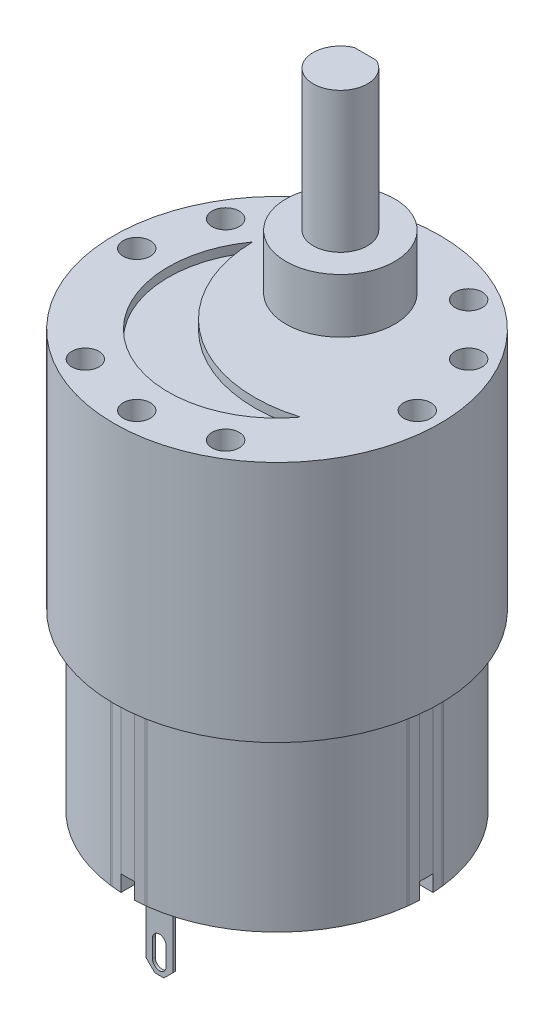
SolidWorks part; units mm, degrees
ref_plane "Front Plane" through (0, 0, 0) normal (0, 0, 1) x (1, 0, 0)
ref_plane "Top Plane" through (0, 0, 0) normal (0, 1, 0) x (1, 0, 0)
ref_plane "Right Plane" through (0, 0, 0) normal (1, 0, 0) x (0, 0, -1)
sketch "Sketch4" plane through (0, 0, 0) normal (0, 1, 0) x (1, 0, 0)
  line L0 (1.199, 9.75) -> (-1.199, 9.75)
  line L1 (6.3399, -16.8465) -> (6.3402, -16.8475)
  line L2 (5.6036, -17.1055) -> (5.6039, -17.1065)
  line L3 (-1.891, -17.9004) -> (-1.8911, -17.9014)
  line L4 (-1.2513, -17.9565) -> (-1.2514, -17.9575)
  line L5 (7.6212, -16.307) -> (7.6216, -16.3079)
  line L6 (-7.4709, -16.3764) -> (-7.4713, -16.3773)
  line L7 (-5.9708, -16.9809) -> (-5.9711, -16.9818)
  line L8 (-3.5022, -17.656) -> (-3.5024, -17.657)
  line L9 (5.1061, -17.2606) -> (5.1064, -17.2616)
  line L10 (-9.1333, -15.5115) -> (-9.1335, -15.5118)
  line L11 (-8.2134, -16.0169) -> (-8.2138, -16.0178)
  line L12 (-5.5614, -17.1193) -> (-5.5617, -17.1203)
  line L13 (-2.0114, -17.8883) -> (-1.9309, -17.8968)
  line L14 (-2.1464, -17.8726) -> (-2.0114, -17.8883)
  line L15 (5.1226, -17.2557) -> (5.1229, -17.2566)
  line L16 (-3.6114, -17.635) -> (-3.5453, -17.6481)
  line L17 (-5.5496, -17.1231) -> (-5.5499, -17.1241)
  line L18 (-0.9209, -17.9764) -> (-0.921, -17.9774)
  line L19 (5.5426, -17.1254) -> (5.5429, -17.1264)
  line L20 (-2.763, -17.7877) -> (-2.7337, -17.7922)
  line L21 (3.3885, -17.6792) -> (3.4863, -17.66)
  line L22 (3.3594, -17.6848) -> (3.3885, -17.6792)
  line L23 (-9.4676, -15.3101) -> (-9.4487, -15.3218)
  circle A0 centre (0, 7) radius 6
  circle A1 centre (7.75, -13.4234) radius 1.5
  circle A2 centre (7.75, 13.4234) radius 1.5
  circle A3 centre (15.5, 0) radius 1.5
  circle A4 centre (0, 0) radius 18
  circle A5 centre (-15.5, 0) radius 1.5
  circle A6 centre (-7.75, -13.4234) radius 1.5
  circle A7 centre (-13.4234, 7.75) radius 1.5
  circle A8 centre (0, -15.5) radius 1.5
  circle A9 centre (-7.75, 13.4234) radius 1.5
  circle A10 centre (13.4234, 7.75) radius 1.5
  arc A11 (-1.199, 9.75) -> (1.199, 9.75) centre (0, 7) ccw
  arc A12 (1.199, 9.75) -> (-1.199, 9.75) centre (0, 7) ccw
  arc A13 (-9.7223, 7.034) -> (9.6912, -7.0767) centre (5.276, 7.2587) ccw
  arc A14 (-9.7223, 7.034) -> (9.6912, -7.0767) centre (0, 0) ccw
  arc A15 (-5.0637, -17.2741) -> (-4.2837, -17.4839) centre (0, 0) ccw
  arc A16 (-0.4816, -17.9946) -> (1.4509, -17.9424) centre (0, 0) ccw
  arc A17 (3.483, -17.6608) -> (5.1064, -17.2616) centre (0, 0) ccw
  arc A18 (-9.1335, -15.5118) -> (-8.2138, -16.0178) centre (0, 0) ccw
  arc A19 (-6.5915, -16.7508) -> (-5.5499, -17.1241) centre (0, 0) ccw
  arc A20 (1.7855, -17.9122) -> (2.9289, -17.7611) centre (0, 0) ccw
  arc A21 (5.9059, -17.0046) -> (7.2979, -16.4553) centre (0, 0) ccw
  spline S0 degree 3 poles (6.3402, -16.8475) (6.6068, -16.7471) (6.813, -16.6627) (6.961, -16.6005) knots 0 0 0 0 0.5 0.5 0.5 0.5
  spline S1 degree 2 poles (6.961, -16.6005) (7.1091, -16.5384) (7.1825, -16.506) knots 0.5 0.5 0.5 1 1 1
  spline S2 degree 3 poles (5.6039, -17.1065) (5.6837, -17.0803) (5.7951, -17.0433) (6.0796, -16.944) (6.2138, -16.895) (6.3402, -16.8475) knots 0 0 0 0 0.5 0.5 1 1 1 1
  spline S3 degree 3 poles (-2.68, -17.8004) (-2.5921, -17.8136) (-2.4727, -17.831) (-2.1706, -17.8703) (-2.027, -17.887) (-1.8911, -17.9014) knots 0 0 0 0 0.5 0.5 1 1 1 1
  spline S4 degree 3 poles (-1.8911, -17.9014) (-1.616, -17.9305) (-1.4189, -17.9458) (-1.2514, -17.9575) knots 0 0 0 0 1 1 1 1
  spline S5 degree 3 poles (8.4939, -15.871) (8.7886, -15.7133) (9.0012, -15.5896) (9.1367, -15.5098) knots 0 0 0 0 0.5 0.5 0.5 0.5
  spline S6 degree 2 poles (9.1367, -15.5098) (9.2722, -15.43) (9.3392, -15.3888) knots 0.5 0.5 0.5 1 1 1
  spline S7 degree 2 poles (7.6216, -16.3079) (7.6938, -16.2747) (7.8368, -16.2055) knots 0 0 0 0.5 0.5 0.5
  spline S8 degree 3 poles (7.8368, -16.2055) (7.9799, -16.1363) (8.2006, -16.028) (8.4939, -15.871) knots 0.5 0.5 0.5 0.5 1 1 1 1
  spline S9 degree 3 poles (-6.5017, -16.7858) (-6.3083, -16.8607) (-6.1327, -16.925) (-5.9711, -16.9818) knots 0 0 0 0 1 1 1 1
  spline S10 degree 3 poles (-4.2837, -17.4839) (-4.0726, -17.5356) (-3.9134, -17.5707) (-3.701, -17.6168) (-3.5993, -17.6378) (-3.5024, -17.657) knots 0 0 0 0 0.5 0.5 1 1 1 1
  spline S11 degree 3 poles (-5.9711, -16.9818) (-5.9059, -17.0047) (-5.8335, -17.0298) (-5.6744, -17.0835) (-5.6102, -17.1045) (-5.5617, -17.1203) knots 0 0 0 0 0.5 0.5 1 1 1 1
  spline S12 degree 2 poles (-1.2514, -17.9575) (-1.0739, -17.9698) (-0.9802, -17.9743) knots 0 0 0 1 1 1
  spline S13 degree 2 poles (-3.5024, -17.657) (-3.286, -17.6999) (-3.1918, -17.7158) knots 0 0 0 1 1 1
  spline S14 degree 2 poles (-7.8335, -16.2072) (-7.7051, -16.2707) (-7.4713, -16.3773) knots 0 0 0 1 1 1
  spline S15 degree 3 poles (-1.4938, -17.9389) (-1.4929, -17.939) (-1.4674, -17.9412) (-1.4343, -17.9438) (-1.3992, -17.9465) (-1.396, -17.9468) (-1.3942, -17.9469) knots 0 0 0 0 0.010494 0.320794 0.64482 1 1 1 1
  spline S16 degree 3 poles (6.7071, -16.7048) (6.7312, -16.6951) (6.7877, -16.6723) (6.7956, -16.669) (6.8001, -16.6672) knots 0 0 0 0 0.427084 1 1 1 1
  spline S17 degree 3 poles (-3.1918, -17.7158) (-3.1514, -17.7229) (-3.0644, -17.7384) (-3.0555, -17.7398) (-3.0507, -17.7406) knots 0 0 0 0 0.463237 1 1 1 1
  spline S18 degree 3 poles (-9.4487, -15.3218) (-9.3817, -15.3629) (-9.2797, -15.4255) (-9.1707, -15.4895) (-9.1333, -15.5115) knots 0 0 0 0 0.656855 1 1 1 1
extrude "Boss-Extrude1" add sketch "Sketch4" against normal blind 26.8 contours A13 A14 | A5 | A7 | A9 | A10 | A2 | A3 | A1 | A8 | A6 | A4 A14 A13 A10 A9 A8 A7 A6 A5 A0 A1 A2 A3 | A0 A12 A11 | L0 A11 | L0 A12 region at (0, 0, -6.9588) region at (0, 0, -9.8504) region at (0.7413, 0, 0.0854) region at (-5.8303, 0, -7) region at (7.75, 0, 13.4234) region at (7.75, 0, -13.4234) region at (15.5, 0, 0) region at (-15.5, 0, 0) region at (-7.75, 0, 13.4234) region at (-13.4234, 0, -7.75) region at (0, 0, 15.5) region at (-7.75, 0, -13.4234) region at (13.4234, 0, -7.75) region at (-4.2506, 0, 5.8479)
extrude "Cut-Extrude1" cut sketch "Sketch4<4>" against normal blind 1 contours A13 A14
sketch "Sketch4<4>" plane through (0, 0, 0) normal (0, 1, 0) x (1, 0, 0) same geometry as "Sketch4"
extrude "Boss-Extrude2" add sketch "Sketch4<5>" along normal blind 6 separate body contours A0 A12 A11 region at (-5.8303, 0, -7)
sketch "Sketch4<5>" plane through (0, 0, 0) normal (0, 1, 0) x (1, 0, 0) same geometry as "Sketch4"
extrude "Boss-Extrude3" add sketch "Sketch4<7>" along normal blind 9.5 contours L0 A12 region at (0, 0, -9.8504)
sketch "Sketch4<7>" plane through (0, 0, 0) normal (0, 1, 0) x (1, 0, 0) same geometry as "Sketch4"
extrude "Boss-Extrude4" add sketch "Sketch4<8>" along normal blind 21.5 contours L0 A11 region at (0, 0, -6.9588)
sketch "Sketch4<8>" plane through (0, 0, 0) normal (0, 1, 0) x (1, 0, 0) same geometry as "Sketch4"
sketch "Sketch5" plane through (0, -26.8, 0) normal (0, -1, 0) x (1, 0, 0)
  line L0 (0.75, -16.4829) -> (1.8083, -16.4006)
  line L1 (1.8083, -16.4006) -> (2, -16.3783)
  line L2 (16.3783, -2) -> (16.4006, -1.8083)
  line L3 (16.4006, -1.8083) -> (16.4829, -0.75)
  line L4 (-16.4829, -0.75) -> (-16.4006, -1.8083)
  line L5 (-16.4006, -1.8083) -> (-16.3783, -2)
  line L6 (-2, -16.3783) -> (-1.8083, -16.4006)
  line L7 (-1.8083, -16.4006) -> (-0.75, -16.4829)
  line L8 (-0.75, 16.4829) -> (-1.8083, 16.4006)
  line L9 (-1.8083, 16.4006) -> (-2, 16.3783)
  line L10 (-16.3783, 2) -> (-16.4006, 1.8083)
  line L11 (-16.4006, 1.8083) -> (-16.4829, 0.75)
  line L12 (16.4829, 0.75) -> (16.4006, 1.8083)
  line L13 (16.4006, 1.8083) -> (16.3783, 2)
  line L14 (2, 16.3783) -> (1.8083, 16.4006)
  line L15 (1.8083, 16.4006) -> (0.75, 16.4829)
  line L16 (-3.3, 0) -> (-3.5, 0)
  line L17 (-1.5, 13) -> (-1.5, 12.7)
  line L18 (1.5, 13) -> (-1.5, 13)
  line L19 (-0.5, 12.7) -> (-0.5, 13)
  line L20 (-1.5, 12.7) -> (1.5, 12.7)
  line L21 (-1.5, -12.7) -> (-1.5, -13)
  line L22 (-0.5, -13) -> (-0.5, -12.7)
  line L23 (-1.5, -13) -> (1.5, -13)
  line L24 (1.5, -12.7) -> (-1.5, -12.7)
  line L25 (0.5, 13) -> (0.5, 12.7)
  line L26 (0.5, -12.7) -> (0.5, -13)
  line L27 (1.5, -13) -> (1.5, -12.7)
  line L28 (1.5, 12.7) -> (1.5, 13)
  line L29 (13.5, -2) -> (13.5, 2)
  line L30 (16.3783, -2) -> (13.5, -2)
  line L31 (2, -13.5) -> (2, -16.3783)
  line L32 (-2, -13.5) -> (2, -13.5)
  line L33 (-2, -16.3783) -> (-2, -13.5)
  line L34 (-13.5, 2) -> (-13.5, -2)
  line L35 (-2, 13.5) -> (-2, 16.3783)
  line L36 (2, 13.5) -> (-2, 13.5)
  line L37 (2, 16.3783) -> (2, 13.5)
  line L38 (13.5, 2) -> (16.3783, 2)
  line L39 (-9, 3.5) -> (-9, -3.5)
  line L40 (-12, 3.5) -> (-9, 3.5)
  line L41 (-12, -3.5) -> (-12, 3.5)
  line L42 (-9, -3.5) -> (-12, -3.5)
  line L43 (-16.3783, 2) -> (-13.5, 2)
  line L44 (-13.5, -2) -> (-16.3783, -2)
  line L45 (10.5999, 0.1001) -> (10.5999, 1.4967)
  line L46 (11.9965, 0.1001) -> (10.5999, 0.1001)
  line L47 (-16.3896, 1.99) -> (-13.51, 1.99)
  line L48 (10.5999, -0.1001) -> (11.9965, -0.1)
  line L49 (10.5999, -1.4966) -> (10.5999, -0.1001)
  line L50 (-13.51, 1.99) -> (-13.51, -1.99)
  line L51 (10.3998, -0.1001) -> (10.3998, -1.4966)
  line L52 (10.3998, 1.4967) -> (10.3998, 0.1001)
  line L53 (-13.51, -1.99) -> (-16.3896, -1.99)
  line L54 (9.0032, -0.1001) -> (10.3998, -0.1001)
  line L55 (-1.99, -16.3896) -> (-1.99, -13.51)
  line L56 (10.3998, 0.1001) -> (9.0032, 0.1001)
  line L57 (0.75, -14.7) -> (0.75, -16.4829)
  line L58 (-0.75, -14.7) -> (0.75, -14.7)
  line L59 (-0.75, -16.4829) -> (-0.75, -14.7)
  line L60 (-14.7, 0.75) -> (-14.7, -0.75)
  line L61 (-16.4829, 0.75) -> (-14.7, 0.75)
  line L62 (-0.75, 14.7) -> (-0.75, 16.4829)
  line L63 (0.75, 14.7) -> (-0.75, 14.7)
  line L64 (0.75, 16.4829) -> (0.75, 14.7)
  line L65 (14.7, 0.75) -> (16.4829, 0.75)
  line L66 (14.7, -0.75) -> (14.7, 0.75)
  line L67 (16.4829, -0.75) -> (14.7, -0.75)
  line L68 (-14.7, -0.75) -> (-16.4829, -0.75)
  line L69 (-7.6212, -16.307) -> (-7.6216, -16.3079)
  line L70 (-3.3592, -17.6838) -> (-3.3594, -17.6848)
  line L71 (1.1897, -17.9606) -> (1.1897, -17.9616)
  line L72 (6.5037, -16.784) -> (6.5041, -16.7849)
  line L73 (9.005, -15.5856) -> (9.0055, -15.5865)
  line L74 (8.2134, -16.0169) -> (8.2138, -16.0178)
  line L75 (3.3616, -17.6833) -> (3.3618, -17.6843)
  line L76 (5.0634, -17.2732) -> (5.0637, -17.2741)
  line L77 (-5.5426, -17.1254) -> (-5.5429, -17.1264)
  line L78 (-0.1334, -17.9995) -> (-0.1334, -18.0005)
  line L79 (5.5496, -17.1231) -> (5.5499, -17.1241)
  line L80 (-4.5567, -17.4147) -> (-4.5233, -17.4233)
  line L81 (-4.1396, -17.5185) -> (-4.0723, -17.5343)
  line L82 (1.9746, -17.8924) -> (2.1464, -17.8726)
  line L83 (0.9802, -17.9743) -> (1.0054, -17.9729)
  line L84 (5.5617, -17.1203) -> (5.5945, -17.1096)
  line L85 (2.357, -17.845) -> (2.3571, -17.846)
  line L86 (2.6556, -17.804) -> (2.68, -17.8004)
  line L87 (0.3013, -17.9985) -> (0.4816, -17.9946)
  line L88 (-1.99, -13.51) -> (1.99, -13.51)
  line L89 (1.99, -13.51) -> (1.99, -16.3896)
  line L90 (16.3896, -1.99) -> (13.51, -1.99)
  line L91 (13.51, -1.99) -> (13.51, 1.99)
  line L92 (13.51, 1.99) -> (16.3896, 1.99)
  line L93 (1.99, 16.3896) -> (1.99, 13.51)
  line L94 (1.99, 13.51) -> (-1.99, 13.51)
  line L95 (-1.99, 13.51) -> (-1.99, 16.3896)
  circle A0 centre (0, 0) radius 3.5
  circle A1 centre (0, 0) radius 3.3
  circle A2 centre (0, 0) radius 1.4
  circle A3 centre (10.4998, 0) radius 1.5
  circle A4 centre (0, 0) radius 18
  arc A5 (2, -16.3783) -> (16.3783, -2) centre (0, 0) ccw
  arc A6 (16.3783, 2) -> (2, 16.3783) centre (0, 0) ccw
  arc A7 (5.891, 2.747) -> (4.9847, 2.3244) centre (5.4378, 2.5357) ccw
  arc A8 (4.7631, -2.75) -> (4.9847, 2.3244) centre (0, 0) ccw
  arc A9 (4.7631, -2.75) -> (5.6292, -3.25) centre (5.1962, -3) ccw
  arc A10 (5.6292, -3.25) -> (5.891, 2.747) centre (0, 0) ccw
  arc A11 (-2.2187, -4.7581) -> (-2.8527, -6.1176) centre (-2.5357, -5.4378) ccw
  arc A12 (-2.8527, -6.1176) -> (2.8527, -6.1176) centre (0, 0) ccw
  arc A13 (2.8527, -6.1176) -> (2.2187, -4.7581) centre (2.5357, -5.4378) ccw
  arc A14 (-2.2187, -4.7581) -> (2.2187, -4.7581) centre (0, 0) ccw
  arc A15 (2.2187, 4.7581) -> (2.8527, 6.1176) centre (2.5357, 5.4378) ccw
  arc A16 (2.8527, 6.1176) -> (-2.8527, 6.1176) centre (0, 0) ccw
  arc A17 (-2.8527, 6.1176) -> (-2.2187, 4.7581) centre (-2.5357, 5.4378) ccw
  arc A18 (2.2187, 4.7581) -> (-2.2187, 4.7581) centre (0, 0) ccw
  arc A19 (-4.9847, 2.3244) -> (-5.891, 2.747) centre (-5.4378, 2.5357) ccw
  arc A20 (-5.891, 2.747) -> (-5.6292, -3.25) centre (0, 0) ccw
  arc A21 (-5.6292, -3.25) -> (-4.7631, -2.75) centre (-5.1962, -3) ccw
  arc A22 (-4.9847, 2.3244) -> (-4.7631, -2.75) centre (0, 0) ccw
  arc A23 (-2, 16.3783) -> (-16.3783, 2) centre (0, 0) ccw
  arc A24 (-16.3783, -2) -> (-2, -16.3783) centre (0, 0) ccw
  arc A25 (-16.4829, 0.75) -> (-16.4829, -0.75) centre (0, 0) ccw
  arc A26 (0.75, 16.4829) -> (-0.75, 16.4829) centre (0, 0) ccw
  arc A27 (-0.75, -16.4829) -> (0.75, -16.4829) centre (0, 0) ccw
  arc A28 (16.4829, -0.75) -> (16.4829, 0.75) centre (0, 0) ccw
  arc A29 (4.2189, -17.4996) -> (5.0637, -17.2741) centre (0, 0) ccw
  arc A30 (-7.2979, -16.4553) -> (-5.5429, -17.1264) centre (0, 0) ccw
  arc A31 (-1.0911, -17.9679) -> (0.3013, -17.9985) centre (0, 0) ccw
  arc A32 (-2.9289, -17.7611) -> (-1.7855, -17.9122) centre (0, 0) ccw
  arc A33 (5.9292, -16.9965) -> (6.5915, -16.7508) centre (0, 0) ccw
  arc A34 (-5.1064, -17.2616) -> (-3.8675, -17.5806) centre (0, 0) ccw
  arc A35 (8.5722, -15.8289) -> (9.1335, -15.5118) centre (0, 0) ccw
  arc A36 (-16.3883, -2.0012) -> (-2.0012, -16.3883) centre (0, 0) ccw
  arc A37 (-1.99, 16.3896) -> (-16.3896, 1.99) centre (0, 0) ccw
  arc A38 (-16.3896, -1.99) -> (-1.99, -16.3896) centre (0, 0) ccw
  arc A39 (1.99, -16.3896) -> (16.3896, -1.99) centre (0, 0) ccw
  arc A40 (16.3896, 1.99) -> (1.99, 16.3896) centre (0, 0) ccw
  spline S0 degree 2 poles (-9.3392, -15.3888) (-9.2715, -15.4305) (-9.1345, -15.5111) knots 0 0 0 0.5 0.5 0.5
  spline S1 degree 3 poles (-9.1345, -15.5111) (-8.9976, -15.5917) (-8.7857, -15.7148) (-8.4939, -15.871) knots 0.5 0.5 0.5 0.5 1 1 1 1
  spline S2 degree 3 poles (-8.4939, -15.871) (-8.1977, -16.0295) (-7.9762, -16.1381) (-7.8346, -16.2065) knots 0 0 0 0 0.5 0.5 0.5 0.5
  spline S3 degree 2 poles (-7.8346, -16.2065) (-7.693, -16.275) (-7.6216, -16.3079) knots 0.5 0.5 0.5 1 1 1
  spline S4 degree 3 poles (-4.8643, -17.3313) (-4.7818, -17.3545) (-4.679, -17.3827) (-4.432, -17.4473) (-4.2935, -17.4822) (-4.1396, -17.5185) knots 0 0 0 0 0.5 0.5 1 1 1 1
  spline S5 degree 3 poles (1.1897, -17.9616) (1.3672, -17.9499) (1.6202, -17.9308) (1.9378, -17.8964) knots 0 0 0 0 1 1 1 1
  spline S6 degree 3 poles (1.9378, -17.8964) (2.09, -17.8799) (2.2404, -17.8617) (2.5375, -17.8219) (2.6621, -17.8034) (2.763, -17.7877) knots 0 0 0 0 0.5 0.5 1 1 1 1
  spline S7 degree 3 poles (6.5041, -16.7849) (6.9064, -16.629) (7.2399, -16.4829) (7.4736, -16.3763) knots 0 0 0 0 1 1 1 1
  spline S8 degree 3 poles (5.9758, -16.9802) (6.0706, -16.9468) (6.1557, -16.916) (6.3071, -16.8601) (6.3981, -16.826) (6.5041, -16.7849) knots 0 0 0 0 0.5 0.5 1 1 1 1
  spline S9 degree 2 poles (8.2138, -16.0178) (8.2866, -15.981) (8.4306, -15.9047) knots 0 0 0 0.5 0.5 0.5
  spline S10 degree 3 poles (8.4306, -15.9047) (8.5747, -15.8284) (8.7674, -15.724) (9.0055, -15.5865) knots 0.5 0.5 0.5 0.5 1 1 1 1
  spline S11 degree 3 poles (9.0055, -15.5865) (9.0625, -15.5535) (9.1383, -15.5093) (9.3263, -15.397) (9.4046, -15.3491) (9.4676, -15.3101) knots 0 0 0 0 0.5 0.5 1 1 1 1
  spline S12 degree 3 poles (3.3618, -17.6843) (3.475, -17.6628) (3.5958, -17.6387) (3.8519, -17.5845) (4.0172, -17.5482) (4.2189, -17.4996) knots 0 0 0 0 0.5 0.5 1 1 1 1
  spline S13 degree 3 poles (-1.4509, -17.9424) (-1.0126, -17.9779) (-0.5731, -17.9972) (-0.1334, -18.0005) knots 0 0 0 0 1 1 1 1
  spline S14 degree 3 poles (5.5499, -17.1241) (5.5985, -17.1083) (5.6642, -17.0868) (5.8296, -17.0311) (5.9059, -17.0048) (5.9758, -16.9802) knots 0 0 0 0 0.5 0.5 1 1 1 1
  spline S15 degree 2 poles (0.921, -17.9774) (1.0189, -17.973) (1.1897, -17.9616) knots 0 0 0 1 1 1
  spline S16 degree 2 poles (-5.1229, -17.2566) (-5.0291, -17.2851) (-4.8643, -17.3313) knots 0 0 0 1 1 1
  spline S17 degree 2 poles (3.0507, -17.7406) (3.0791, -17.7358) (3.1358, -17.7258) knots 0 0 0 0.5 0.5 0.5
  spline S18 degree 3 poles (3.1358, -17.7258) (3.1926, -17.7157) (3.268, -17.7021) (3.3618, -17.6843) knots 0.5 0.5 0.5 0.5 1 1 1 1
  spline S19 degree 2 poles (7.4736, -16.3763) (7.7073, -16.2696) (7.8335, -16.2072) knots 0 0 0 1 1 1
  spline S20 degree 3 poles (3.1918, -17.7158) (3.1975, -17.7147) (3.2089, -17.7126) (3.2706, -17.7016) (3.3289, -17.6905) (3.3421, -17.6879) knots 0 0 0 0 0.443284 0.872983 1 1 1 1
  spline S21 degree 3 poles (3.3743, -17.6818) (3.393, -17.6783) (3.4188, -17.6735) (3.4559, -17.6661) (3.466, -17.664) knots 0 0 0 0 0.725405 1 1 1 1
  dimension "D1" = 0.01
  dimension "D2" = 0.01
extrude "Cut-Extrude2" cut sketch "Sketch4<9>" against normal blind 6 contours A9 | A2 | A10 | A3 | A1 | A8 | A6 | A5 | A7 region at (7.75, 0, 13.4234) region at (7.75, 0, -13.4234) region at (15.5, 0, 0) region at (-15.5, 0, 0) region at (-7.75, 0, 13.4234) region at (-13.4234, 0, -7.75) region at (0, 0, 15.5) region at (-7.75, 0, -13.4234) region at (13.4234, 0, -7.75)
sketch "Sketch4<9>" plane through (0, 0, 0) normal (0, 1, 0) x (1, 0, 0) same geometry as "Sketch4"
extrude "Boss-Extrude6" add sketch "Sketch5" along normal blind 19.2 contours L44 A24 L33 L32 L31 A5 L30 L29 L38 A6 L37 L36 L35 A23 L43 L34 A19 A22 A21 A20 A15 A18 A17 A16 A11 A14 A13 A12 L39 L42 L41 L40 L27 L23 L21 L24 L28 L20 L17 region at (2.4632, -26.8, -14.9392)
extrude "Boss-Extrude8" add sketch "Sketch5<6>" along normal blind 21.7 contours L48 A3 L46 L45 L52 L56 L54 L51 L49 region at (10.4998, -26.8, 0)
sketch "Sketch5<6>" plane through (0, -26.8, 0) normal (0, -1, 0) x (1, 0, 0) same geometry as "Sketch5"
extrude "Boss-Extrude9" add sketch "Sketch5<7>" along normal blind 21.5 contours L49 A3 L48 | L54 A3 L51 | L52 A3 L56 | L46 A3 L45 region at (11.1806, -26.8, 0.6808) region at (9.8191, -26.8, 0.6808) region at (11.1806, -26.8, -0.6807) region at (9.8191, -26.8, -0.6807)
sketch "Sketch5<7>" plane through (0, -26.8, 0) normal (0, -1, 0) x (1, 0, 0) same geometry as "Sketch5"
extrude "Boss-Extrude10" add sketch "Sketch5<8>" along normal blind 17.4 contours L61 A25 L68 L60 | L64 A26 L62 L63 | L67 A28 L65 L66 | L59 A27 L57 L58 region at (0, -26.8, -15.5972) region at (15.5972, -26.8, 0) region at (-15.5972, -26.8, 0) region at (0, -26.8, 15.5972)
sketch "Sketch5<8>" plane through (0, -26.8, 0) normal (0, -1, 0) x (1, 0, 0) same geometry as "Sketch5"
extrude "Boss-Extrude11" add sketch "Sketch5<10>" along normal blind 19.2 contours L60 L68 L4 L5 L44 L34 L43 L10 L11 L61 | L15 L64 L63 L62 L8 L9 L35 L36 L37 L14 | L3 L67 L66 L65 L12 L13 L38 L29 L30 L2 | L7 L59 L58 L57 L0 L1 L31 L32 L33 L6 region at (0.7997, -26.8, -15.5915) region at (14.9448, -26.8, -1.9403) region at (-16.3407, -26.8, -1.8934) region at (1.9403, -26.8, 14.9448)
sketch "Sketch5<10>" plane through (0, -26.8, 0) normal (0, -1, 0) x (1, 0, 0) same geometry as "Sketch5"
extrude "Boss-Extrude16" add sketch "Sketch5<15>" along normal blind 28.5 contours L23 L27 L24 L26 | L26 L24 L22 L23 | L22 L24 L21 L23 | L17 L20 L19 L18 | L25 L18 L19 L20 | L20 L28 L18 L25 region at (-1, -26.8, 12.85) region at (0, -26.8, 12.85) region at (1, -26.8, 12.85) region at (-1, -26.8, -12.85) region at (0, -26.8, -12.85) region at (1, -26.8, -12.85)
sketch "Sketch5<15>" plane through (0, -26.8, 0) normal (0, -1, 0) x (1, 0, 0) same geometry as "Sketch5"
sketch "Sketch9" plane through (0, 0, 13) normal (0, 0, 1) x (1, 0, 0)
  line L0 (0, -54.1) -> (0, -52.1) construction
  line L1 (-0.75, -54.1) -> (-0.75, -52.1)
  line L2 (0.75, -54.1) -> (0.75, -52.1)
  line L3 (1.5, -55.3) -> (1.5, -46) construction
  line L4 (-1.5, -55.3) -> (-1.5, -46) construction
  line L5 (1.5, -55.3) -> (-1.5, -55.3) construction
  arc A0 (-0.75, -54.1) -> (0.75, -54.1) centre (0, -54.1) ccw
  arc A1 (0.75, -52.1) -> (-0.75, -52.1) centre (0, -52.1) ccw
  point P2 (0, -53.1)
  dimension "D3" = 0.75
  dimension "D1" = 2
  dimension "D2" = 1.2
extrude "Cut-Extrude4" cut sketch "Sketch9" against normal blind 28.5
extrude "Boss-Extrude12" add sketch "Sketch5<11>" along normal blind 25.2 contours A1 A2 | A1 A0 region at (0, -26.8, 3.401) region at (0, -26.8, 3.2067)
sketch "Sketch5<11>" plane through (0, -26.8, 0) normal (0, -1, 0) x (1, 0, 0) same geometry as "Sketch5"
extrude "Boss-Extrude13" add sketch "Sketch5<12>" along normal blind 25 contours A2 region at (0, -26.8, 0)
sketch "Sketch5<12>" plane through (0, -26.8, 0) normal (0, -1, 0) x (1, 0, 0) same geometry as "Sketch5"
extrude "Boss-Extrude14" add sketch "Sketch5<13>" along normal blind 16 contours A22 A19 A20 A21 | A18 A15 A16 A17 | A9 A10 A7 A8 | A14 A11 A12 A13 region at (5.7128, -26.8, -0.2494) region at (0, -26.8, -5.7428) region at (0, -26.8, 5.7428) region at (-5.7128, -26.8, -0.2494)
sketch "Sketch5<13>" plane through (0, -26.8, 0) normal (0, -1, 0) x (1, 0, 0) same geometry as "Sketch5"
extrude "Boss-Extrude15" add sketch "Sketch5<14>" along normal blind 17 contours L42 L39 L40 L41 region at (-10.5, -26.8, 0)
sketch "Sketch5<14>" plane through (0, -26.8, 0) normal (0, -1, 0) x (1, 0, 0) same geometry as "Sketch5"
sketch "Sketch8" plane through (0, 0, -13) normal (0, 0, -1) x (-1, 0, 0)
  line L1 (1.5, -54.3) -> (0.5, -55.3)
  line L2 (-1.5, -55.3) -> (1.5, -55.3) construction
  line L4 (0.5, -55.3) -> (1.5, -55.3)
  line L11 (1.5, -54.3) -> (1.5, -55.3)
  line L12 (1.5, -55.3) -> (1.5, -46) construction
  line L13 (0, -55.3) -> (0, -54.2286) construction
  line L14 (-0.5, -55.3) -> (-1.5, -55.3)
  line L15 (-1.5, -54.3) -> (-1.5, -55.3)
  line L16 (-1.5, -54.3) -> (-0.5, -55.3)
  dimension "D1" = 1
  dimension "D2" = 1
extrude "Cut-Extrude3" cut sketch "Sketch8" against normal blind 28.5
sketch "Sketch11" [suppressed] plane through (0, -46, 0) normal (0, -1, 0) x (1, 0, 0)
  line L24 (-13.51, -1.99) -> (-16.3896, -1.99)
  line L25 (-1.99, -16.3896) -> (-1.99, -13.51)
  line L26 (-1.99, -13.51) -> (1.99, -13.51)
  line L27 (1.99, -13.51) -> (1.99, -16.3896)
  line L28 (16.3896, -1.99) -> (13.51, -1.99)
  line L29 (13.51, -1.99) -> (13.51, 1.99)
  line L30 (13.51, 1.99) -> (16.3896, 1.99)
  line L31 (1.99, 16.3896) -> (1.99, 13.51)
  line L32 (1.99, 13.51) -> (-1.99, 13.51)
  line L33 (-1.99, 13.51) -> (-1.99, 16.3896)
  line L34 (-16.3896, 1.99) -> (-13.51, 1.99)
  line L35 (-13.51, 1.99) -> (-13.51, -1.99)
  line L36 (-13.51, -1.99) -> (-16.3896, -1.99)
  line L37 (-1.99, -16.3896) -> (-1.99, -13.51)
  line L38 (-1.99, -13.51) -> (1.99, -13.51)
  line L39 (1.99, -13.51) -> (1.99, -16.3896)
  line L40 (16.3896, -1.99) -> (13.51, -1.99)
  line L41 (13.51, -1.99) -> (13.51, 1.99)
  line L42 (13.51, 1.99) -> (16.3896, 1.99)
  line L43 (1.99, 16.3896) -> (1.99, 13.51)
  line L44 (1.99, 13.51) -> (-1.99, 13.51)
  line L45 (-1.99, 13.51) -> (-1.99, 16.3896)
  line L46 (-16.3896, 1.99) -> (-13.51, 1.99)
  line L47 (-13.51, 1.99) -> (-13.51, -1.99)
  arc A8 (-16.3896, -1.99) -> (-1.99, -16.3896) centre (0, 0) ccw
  arc A9 (1.99, -16.3896) -> (16.3896, -1.99) centre (0, 0) ccw
  arc A10 (16.3896, 1.99) -> (1.99, 16.3896) centre (0, 0) ccw
  arc A11 (-1.99, 16.3896) -> (-16.3896, 1.99) centre (0, 0) ccw
  arc A12 (-16.3896, -1.99) -> (-1.99, -16.3896) centre (0, 0) ccw
  arc A13 (1.99, -16.3896) -> (16.3896, -1.99) centre (0, 0) ccw
  arc A14 (16.3896, 1.99) -> (1.99, 16.3896) centre (0, 0) ccw
  arc A15 (-1.99, 16.3896) -> (-16.3896, 1.99) centre (0, 0) ccw
  dimension "D1" = 0.01
extrude "Boss-Extrude20" [suppressed] add sketch "Sketch11" along normal blind 2.8 separate body
